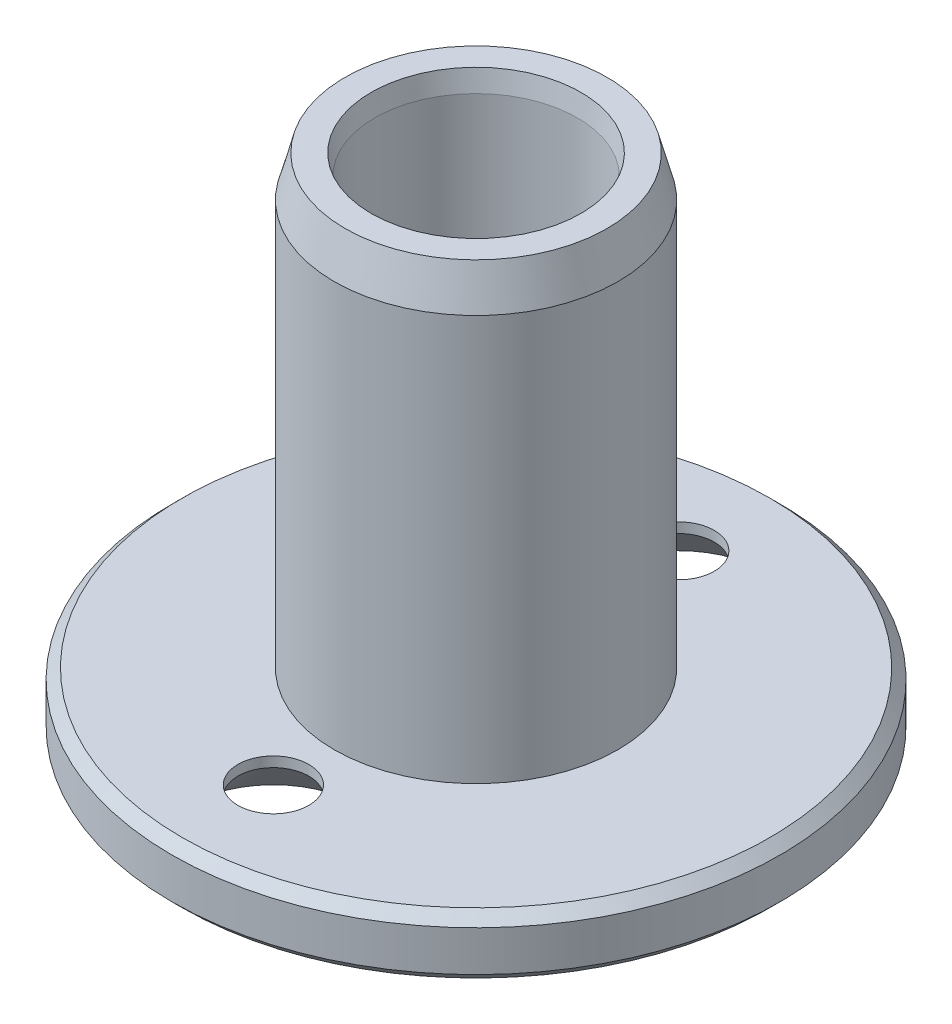
SolidWorks part; units mm, degrees
material "黄铜"
ref_plane "前视基准面" through (0, 0, 0) normal (0, 0, 1) x (1, 0, 0)
ref_plane "上视基准面" through (0, 0, 0) normal (0, 1, 0) x (1, 0, 0)
ref_plane "右视基准面" through (0, 0, 0) normal (1, 0, 0) x (0, 0, -1)
sketch "草图1" plane through (0, 0, 0) normal (0, 1, 0) x (1, 0, 0)
  circle A0 centre (0, 0) radius 15
  circle A1 centre (0, 0) radius 7
  circle A2 centre (0, 0) radius 5
  dimension "法兰直径" = 30
  dimension "外径" = 14
  dimension "内径" = 10
extrude "凸台-拉伸1" add sketch "草图1" along normal blind 3 contours A0 | A2
extrude "凸台-拉伸2" add sketch "草图1<3>" along normal blind 25 contours A1 | A2
sketch "草图1<3>" plane through (0, 0, 0) normal (0, 1, 0) x (1, 0, 0) same geometry as "草图1"
sketch "草图2" plane through (0, 0, 0) normal (0, -1, 0) x (1, 0, 0)
  circle A0 centre (0, 10) radius 4.25
  circle A1 centre (0, 10) radius 1.75
  circle A2 centre (0, 0) radius 10 construction
  dimension "D1" = 8.5
  dimension "螺丝孔径" = 3.5
  dimension "安装孔分布直径" = 20
extrude "切除-拉伸1" cut sketch "草图2" against normal through all contours A1
chamfer "倒角1" distance 2.5 angle 45 1 edges at (0, 0, 8.25)
mirror "两孔" about plane through (0, 0, 0) normal (0, 0, 1) of "切除-拉伸1", "倒角1"
pattern_circular "四孔" [suppressed] count 4 over 360 reverse direction yes of bodies 108
chamfer "倒角2" distance 2 angle 15 1 edges at (0, 25, 7) first distance on face at (0, 3, 7)
chamfer "倒角4" distance 1 angle 10 2 edges at (0, 0, 5) (0, 25, 5) first distance on face at (0, 0, 5)
chamfer "倒角5" distance 0.5 angle 45 2 edges at (0, 0, 15) (0, 3, 15)
other "冻结***"
